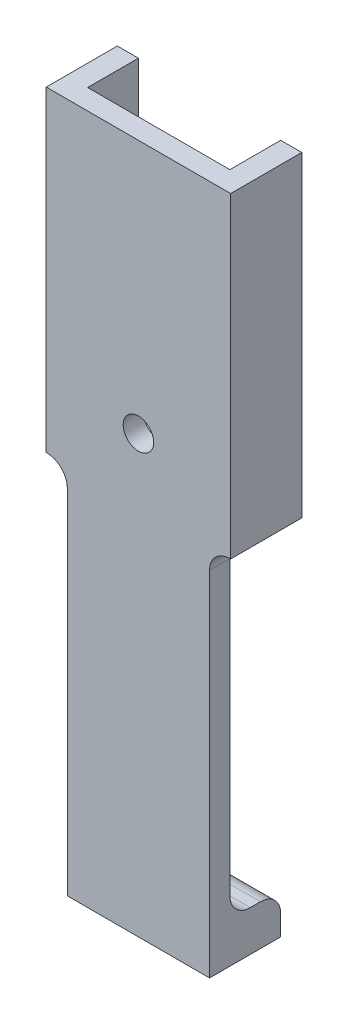
SolidWorks part; units mm, degrees
ref_plane "Front Plane" through (0, 0, 0) normal (0, 0, 1) x (1, 0, 0)
ref_plane "Top Plane" through (0, 0, 0) normal (0, 1, 0) x (1, 0, 0)
ref_plane "Right Plane" through (0, 0, 0) normal (1, 0, 0) x (0, 0, -1)
other "Configuration Table"
sketch "Sketch2" plane through (0, 0, 0) normal (0, 0, 1) x (1, 0, 0)
  line L1 (-7, -15.5) -> (7, -15.5)
  line L2 (-7, -15.5) -> (-7, -52.4)
  line L3 (-7, -52.4) -> (7, -52.4)
  line L4 (-7, 15.5) -> (-7, -15.5)
  line L5 (-7, -15.5) -> (7, -15.5)
  line L6 (7, -15.5) -> (7, 15.5)
  line L7 (7, 15.5) -> (-7, 15.5)
  line L8 (-7, 15.5) -> (-7, -15.5)
  line L9 (-7, -15.5) -> (7, -15.5)
  line L10 (7, -15.5) -> (7, 15.5)
  line L11 (7, 15.5) -> (-7, 15.5)
  line L12 (7, -15.5) -> (7, -52.4)
  circle A0 centre (0, -9.5) radius 1.5
  arc M5 (-1.7, -9.5) -> (1.7, -9.5) centre (0, -9.5) cw
  arc M6 (1.7, -9.5) -> (-1.7, -9.5) centre (0, -9.5) cw
  line M7 (-7, 15.5) -> (-7, -15.5)
  line M8 (-7, -15.5) -> (7, -15.5)
  line M9 (7, -15.5) -> (7, 15.5)
  line M10 (7, 15.5) -> (-7, 15.5)
  dimension "D2" = 3
  dimension "D1" = 0
extrude "Boss-Extrude1" add sketch "Sketch2" along normal blind 2 contours M10 M7 M8 M9 M6 M5 | A0 M5 M6 | L12 L2 L3 M8 region at (0, 0.203, 0) region at (0, -33.95, 0) region at (0, -7.8481, 0)
sketch "Sketch3" plane through (0, 0, 0) normal (0, 0, -1) x (-1, 0, 0)
  line L0 (-7, -52.4) -> (-7, 15.5) construction
  line L1 (-7, -48.4) -> (7, -48.4)
  line L2 (-7, -48.4) -> (-7, -52.4)
  line L3 (-7, -52.4) -> (7, -52.4)
  line L4 (7, -48.4) -> (7, -52.4)
  line L5 (7, 15.5) -> (7, -52.4) construction
  line L6 (-7, -52.4) -> (19, -52.4) construction
  dimension "D1" = 4
extrude "Boss-Extrude2" add sketch "Sketch3" along normal blind 5
sketch "Sketch4" plane through (0, -52.4, 0) normal (0, -1, 0) x (1, 0, 0)
  line L0 (0, 2) -> (0, -5) construction
  line L1 (-7, -1.5) -> (7, -1.5) construction
  line L4 (-7, 2) -> (-7, -5)
  line L5 (-7, -5) -> (7, -5)
  line L6 (7, -5) -> (7, 2)
  line L7 (7, 2) -> (-7, 2)
  line L8 (-7, 2) -> (-7, -5)
  line L9 (-7, -5) -> (7, -5)
  line L10 (7, -5) -> (7, 2)
  line L11 (7, 2) -> (-7, 2)
  circle A0 centre (-3.5, -1.5) radius 1
  circle A1 centre (3.5, -1.5) radius 1
  dimension "D2" = 2
  dimension "D3" = 3.5
  dimension "D1" = 0
extrude "Cut-Extrude1" cut sketch "Sketch4" against normal up to surface (4 mm away) contours A0 | A1 region at (-3.5, -52.4, -1.5) region at (3.5, -52.4, -1.5) up to face at (0, -48.4, -2.5)
sketch "Sketch5" plane through (0, 0, 0) normal (0, 0, -1) x (-1, 0, 0)
  line L0 (7, 15.5) -> (-7, 15.5) construction
  line L1 (-7.075, -15.5) -> (7.075, -15.5)
  line L2 (-7.075, -15.5) -> (-7.075, 15.5)
  line L3 (-7.075, 15.5) -> (7.075, 15.5)
  line L4 (7.075, -15.5) -> (7.075, 15.5)
  line L5 (-7.075, -15.5) -> (7.075, 15.5) construction
  line L6 (-7.075, 15.5) -> (7.075, -15.5) construction
  line L7 (0, 15.5) -> (0, -15.5) construction
  line L8 (7.075, 15.5) -> (9.075, 15.5)
  line L9 (7.075, 15.5) -> (7.075, -15.65)
  line L10 (7.075, -15.65) -> (9.075, -15.65)
  line L11 (9.075, 15.5) -> (9.075, -15.65)
  line L12 (-7.075, 15.5) -> (-7.075, -15.65)
  line L13 (-7.075, -15.65) -> (-9.075, -15.65)
  line L14 (-7.075, 15.5) -> (-9.075, 15.5)
  line L15 (-9.075, 15.5) -> (-9.075, -15.65)
  line L16 (7.075, -15.65) -> (7, -15.65)
  line L17 (7, 15.5) -> (7, -48.4) construction
  line L18 (-7.075, -15.65) -> (-7, -15.65)
  line L19 (-7, -48.4) -> (-7, 15.5) construction
  point P0 (0, 0)
  line M3 (-7, 15.5) -> (-7, -48.4)
  line M5 (7, -48.4) -> (7, 15.5)
  dimension "D1" = 14.15
  dimension "D2" = 31.15
  dimension "D3" = 2
extrude "Boss-Extrude3" add sketch "Sketch5" along normal blind 5 and the other way up to surface (2 mm away) contours L14 L15 L13 L12 L2 | L11 L8 L4 L9 L10 | L1 L4 L3 M5 | L3 L2 L1 M3 | L12 L18 L1 M3 | L16 L9 L1 M5 region at (7.0375, 0, 0) region at (8.075, -0.075, 0) region at (7.0375, -15.575, 0) region at (-7.0375, 0, 0) region at (-7.0375, -15.575, 0) region at (-8.075, -0.075, 0) other way up to face at (0, -18.45, 2)
fillet "Fillet1" radius 2 4 edges at (0, -48.4, 0) (0, -48.4, -5) (7, -15.65, 1) (-7, -15.65, 1)
equation "\"F\"= 2'Fillet radius"
equation "\"D1@Fillet1\"=\"F\""
equation "\"C\"= 0.15'Clearance gap"
equation "\"D1@Sketch5\"=14+\"C\""
equation "\"D2@Sketch5\"=31+\"C\""
